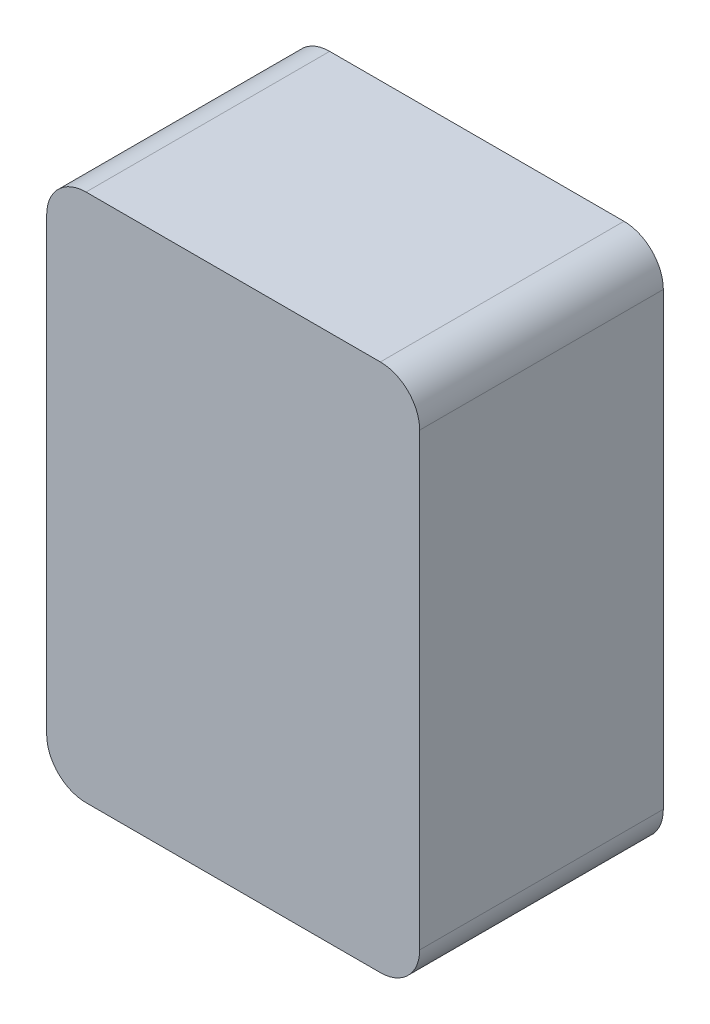
SolidWorks part; units mm, degrees
ref_plane "Front Plane" through (0, 0, 0) normal (0, 0, 1) x (1, 0, 0)
ref_plane "Top Plane" through (0, 0, 0) normal (0, 1, 0) x (1, 0, 0)
ref_plane "Right Plane" through (0, 0, 0) normal (1, 0, 0) x (0, 0, -1)
sketch "Sketch1" plane through (0, 0, 0) normal (0, 0, 1) x (1, 0, 0)
  line L12 (-41.8589, 76.8356) -> (36.6581, 76.8356)
  line L13 (46.6581, 66.8356) -> (46.6581, -53.2671)
  line L14 (-51.8589, 66.8356) -> (-51.8589, -53.2671)
  line L15 (-41.8589, -63.2671) -> (36.6581, -63.2671)
  line L16 (-41.8589, 77.3356) -> (36.6581, 77.3356)
  line L17 (47.1581, 66.8356) -> (47.1581, -53.2671)
  line L18 (-41.8589, -63.7671) -> (36.6581, -63.7671)
  line L19 (-52.3589, 66.8356) -> (-52.3589, -53.2671)
  arc A12 (36.6581, 76.8356) -> (46.6581, 66.8356) centre (36.6581, 66.8356) cw
  arc A13 (-41.8589, 76.8356) -> (-51.8589, 66.8356) centre (-41.8589, 66.8356) ccw
  arc A14 (36.6581, -63.2671) -> (46.6581, -53.2671) centre (36.6581, -53.2671) ccw
  arc A15 (-41.8589, -63.2671) -> (-51.8589, -53.2671) centre (-41.8589, -53.2671) cw
  arc A16 (36.6581, 77.3356) -> (47.1581, 66.8356) centre (36.6581, 66.8356) cw
  arc A17 (36.6581, -63.7671) -> (47.1581, -53.2671) centre (36.6581, -53.2671) ccw
  arc A18 (-41.8589, -63.7671) -> (-52.3589, -53.2671) centre (-41.8589, -53.2671) cw
  arc A19 (-41.8589, 77.3356) -> (-52.3589, 66.8356) centre (-41.8589, 66.8356) ccw
  dimension "D1" = 0.5
extrude "Boss-Extrude1" add sketch "Sketch1" along normal blind 65 contours L19 A18 L18 A17 L17 A16 L16 A19
extrude "Cut-Extrude1" cut sketch "Sketch1<4>" along normal blind 64.5 contours L12 A12 region at (-2.6004, 6.7842, 0)
sketch "Sketch1<4>" plane through (0, 0, 0) normal (0, 0, 1) x (1, 0, 0) same geometry as "Sketch1"
